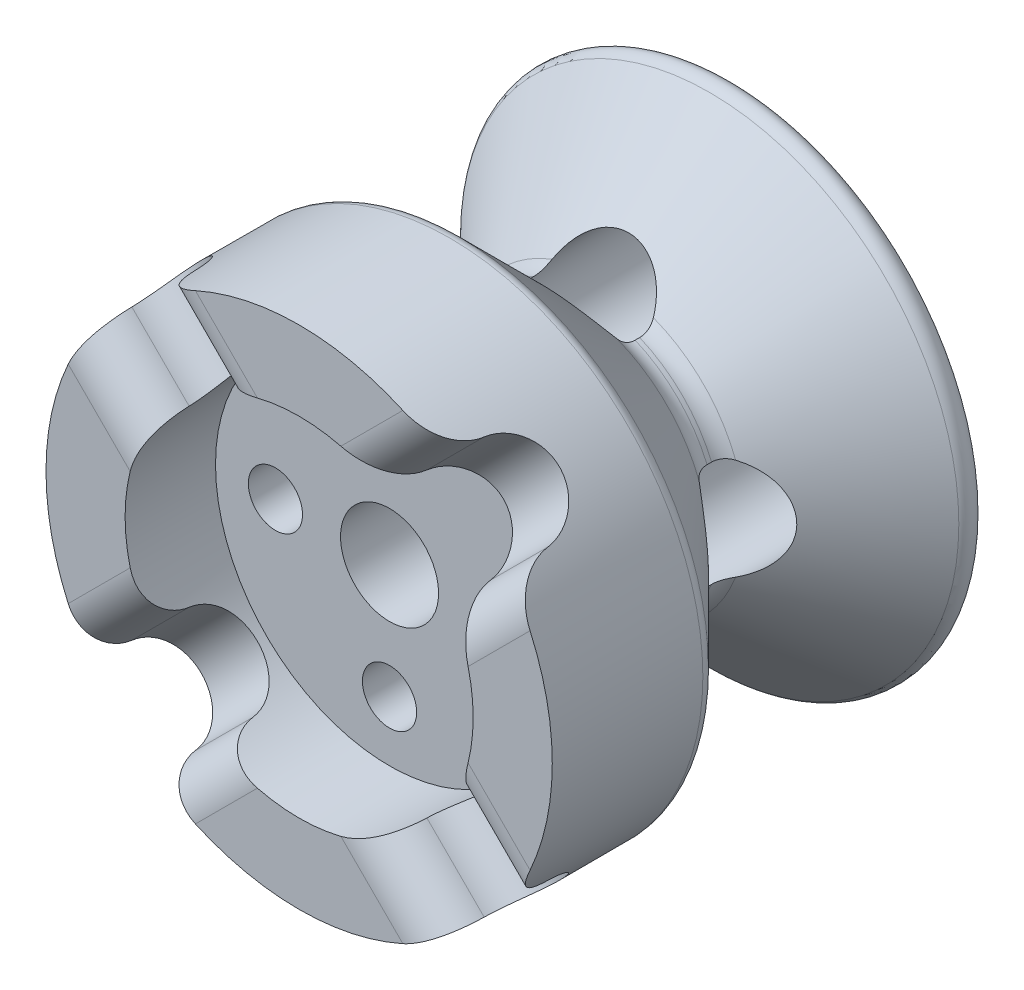
SolidWorks part; units mm, degrees
material "Polymaker PLA"
ref_plane "Front Plane" through (0, 0, 0) normal (0, 0, 1) x (1, 0, 0)
ref_plane "Top Plane" through (0, 0, 0) normal (0, 1, 0) x (1, 0, 0)
ref_plane "Right Plane" through (0, 0, 0) normal (1, 0, 0) x (0, 0, -1)
sketch "Sketch1" plane through (0, 0, 0) normal (0, 0, 1) x (1, 0, 0)
  circle A1 centre (0, 0) radius 14.224
  circle A2 centre (0, 0) radius 9.779
  circle A3 centre (0, 0) radius 9.779
  dimension "D2" = 28.448
  dimension "D1" = 0.254
extrude "Boss-Extrude1" add sketch "Sketch1" against normal up to surface (5.08 mm away)
ref_plane "SCREW_PLANE" through (0, 0, -12.192) normal (0, 0, 1) x (1, 0, 0)
sketch "Sketch2" plane through (0, 0, 0) normal (0, 1, 0) x (1, 0, 0)
  line L0 (-2.754, 5.08) -> (-2.754, 21.234)
  line L1 (-2.5, 5.08) -> (-2.5, 21.234) construction
  line L2 (2, 21.234) -> (-2, 21.234) construction
  line L3 (-2.754, 5.08) -> (-14.224, 5.08)
  line L4 (0, 0) -> (0, 21.234) construction
  line L5 (0, 16.034) -> (-14.224, 16.034) construction
  line L6 (23.1, 16.034) -> (-23.1, 16.034) construction
  line L7 (0, 14.1527) -> (-9.1944, 14.1527) construction
  line L8 (-9.1944, 14.1527) -> (-9.1944, 5.08) construction
  line L9 (-9.1944, 13.0333) -> (-9.1944, 12.5578) construction
  line L10 (-7.62, 16.161) -> (-7.62, 15.907)
  line L11 (-7.992, 15.009) -> (-14.0008, 9.0001)
  line L12 (-14.224, 8.4613) -> (-14.224, 5.08)
  line L13 (-7.992, 17.059) -> (-14.0008, 23.0679)
  line L14 (-13.462, 24.3687) -> (-5.8887, 24.3687)
  line L15 (0, 21.234) -> (-5.8887, 21.234) construction
  arc A0 (-2.754, 21.234) -> (-5.8887, 24.3687) centre (-5.8887, 21.234) ccw
  arc A1 (-7.62, 15.907) -> (-7.992, 15.009) centre (-8.89, 15.907) cw
  arc A2 (-7.62, 16.161) -> (-7.992, 17.059) centre (-8.89, 16.161) ccw
  arc A4 (-14.0008, 23.0679) -> (-13.462, 24.3687) centre (-13.462, 23.6067) cw
  arc A5 (-14.0008, 9.0001) -> (-14.224, 8.4613) centre (-13.462, 8.4613) ccw
  point P24 (-7.62, 16.034)
  point P34 (-7.62, 16.034)
  point P45 (-15.3016, 24.3687)
  dimension "D3" = 1.27
  dimension "D4" = 0.254
  dimension "D5" = 0.762
  dimension "D2" = 7.62
  dimension "D6" = 0.254
  dimension "D1" = 45
revolve "Revolve1" add sketch "Sketch2" angle 360 about L4
sketch "Sketch3" plane through (0, 0, -12.192) normal (0, 0, 1) x (1, 0, 0)
  line L0 (0, -6.4131) -> (0, 6.4131) construction
  circle A0 centre (0, -6.4131) radius 2.7813 construction
  circle A1 centre (0, -6.4131) radius 2.7813 construction
  circle A2 centre (0, -6.4131) radius 3.0353
  circle A3 centre (0, -6.4131) radius 1.524
  circle A4 centre (0, 0) radius 6.4131 construction
  dimension "D2" = 3.048
  dimension "D1" = 0.254
extrude "Cut-Extrude1" cut sketch "Sketch3" against normal through all contours A2
extrude "Cut-Extrude2" cut sketch "Sketch3<3>" along normal through all contours A3
sketch "Sketch3<3>" plane through (0, 0, -12.192) normal (0, 0, 1) x (1, 0, 0) same geometry as "Sketch3"
ref_axis "CENTER_AXIS" through (0, 0, -22.2957) along (0, 0, 1)
pattern_circular "CirPattern1" count 4 over 360 about axis through (0, 0, -22.2957) along (0, 0, 1) of "Cut-Extrude2", "Cut-Extrude1"
ref_plane "SET_SCREW_PLANE_1" through (0, 0, 0) normal (-0.7071, -0.7071, 0) x (0, 0, 1)
ref_plane "SET_SCREW_PLANE_2" through (0, 0, -2.032) normal (0, 0, -1) x (-1, 0, 0)
ref_axis "SET_SCREW_AXIS" through (12.1, -12.1, -2.032) along (-0.7071, 0.7071, 0)
ref_plane "SET_SCREW_PLANE_3" through (0, 0, 0) normal (-0.7071, 0.7071, 0) x (0.7071, 0.7071, 0)
sketch "Sketch5" plane through (0, 0, 0) normal (-0.7071, 0.7071, 0) x (0.7071, 0.7071, 0)
  circle A0 centre (0, 2.032) radius 2.54
  dimension "D1" = 5.08
extrude "Cut-Extrude3" cut sketch "Sketch5" along normal through all
fillet "Fillet3" radius 2.54 2 edges at (-7.3375, 9.4928, 0) (-9.4928, 7.3375, 0)
pattern_circular "CirPattern3" count 4 over 360 about axis through (0, 0, -22.2957) along (0, 0, 1) of "Cut-Extrude3", "Fillet3"
sketch "Sketch6" plane through (0, 0, -12.192) normal (0, 0, 1) x (1, 0, 0)
  line L0 (0, 0) -> (-6.4131, 0) construction
  circle A6 centre (-6.4131, 0) radius 3.0353
  circle A7 centre (0, -6.4131) radius 3.0353 construction
sketch "Sketch7" plane through (0, 0, -16.034) normal (0, 0, -1) x (-1, 0, 0)
  line L0 (0, 0) -> (6.4131, 0) construction
  circle A0 centre (6.4131, 0) radius 3.0353 construction
  circle A1 centre (6.4131, 0) radius 3.0353 construction
  circle A2 centre (8.4045, 0) radius 5.0267
loft "Cut-Loft1" [suppressed] cut profiles "Sketch7", "Sketch6"
ref_plane "STRING_CENTER_PLANE" through (0, 0, -16.034) normal (0, 0, -1) x (-1, 0, 0)
sketch "STRING_PATH_MIN" plane through (0, 0, -16.034) normal (0, 0, -1) x (-1, 0, 0)
  line L0 (-7.0153, -2.975) -> (-7.0153, 2.975)
  line L1 (-2.975, 7.0153) -> (2.975, 7.0153)
  line L2 (7.0153, 2.975) -> (7.0153, -2.975)
  line L3 (2.975, -7.0153) -> (-2.975, -7.0153)
  arc A0 (7.0153, 2.975) -> (2.975, 7.0153) centre (0, 0) ccw
  arc A1 (7.0153, 2.975) -> (2.975, 7.0153) centre (0, 0) ccw
  arc A2 (2.975, -7.0153) -> (7.0153, -2.975) centre (0, 0) ccw
  arc A3 (2.975, -7.0153) -> (7.0153, -2.975) centre (0, 0) ccw
  arc A4 (-7.0153, -2.975) -> (-2.975, -7.0153) centre (0, 0) ccw
  arc A5 (-7.0153, -2.975) -> (-2.975, -7.0153) centre (0, 0) ccw
  arc A6 (-2.975, 7.0153) -> (-7.0153, 2.975) centre (0, 0) ccw
  arc A7 (-2.975, 7.0153) -> (-7.0153, 2.975) centre (0, 0) ccw
